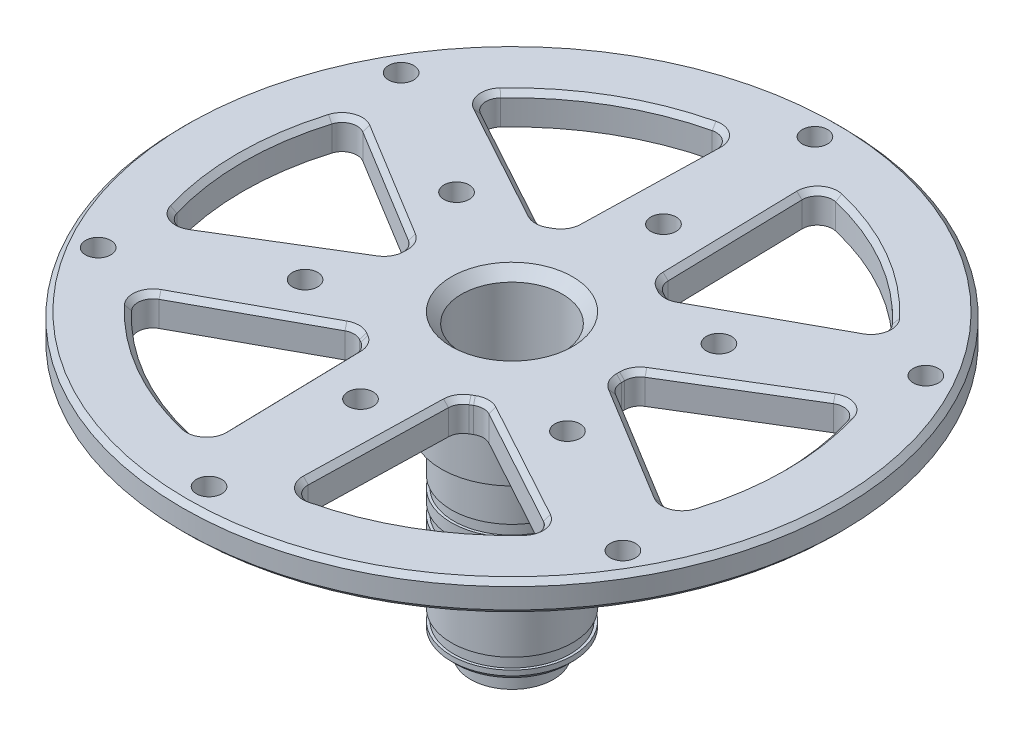
SolidWorks part; units mm, degrees
ref_plane "Front Plane" through (0, 0, 0) normal (0, 0, 1) x (1, 0, 0)
ref_plane "Top Plane" through (0, 0, 0) normal (0, 1, 0) x (1, 0, 0)
ref_plane "Right Plane" through (0, 0, 0) normal (1, 0, 0) x (0, 0, -1)
ref_axis "Axis1" through (0, 0, 0) along (0, 1, 0)
sketch "Sketch2" plane through (0, 0, 0) normal (0, 0, 1) x (1, 0, 0)
  line L0 (0, 0) -> (0, -45684.8392) construction
  line L1 (-4, 10) -> (-4, -6.5)
  line L2 (-4, -6.5) -> (-3.1, -6.5)
  line L3 (-3.1, -6.5) -> (-3.1, -9.5)
  line L4 (-3.1, -9.5) -> (-4.1, -9.5)
  line L5 (-4.1, -9.5) -> (-4.1, -7.5)
  line L6 (-4.1, -7.5) -> (-6, -7.5)
  line L7 (-6, -7.5) -> (-6, 10)
  line L9 (-11.5, -12.5) -> (11.5, -12.5) construction
  line L18 (-7, 17) -> (-7, 10)
  line L20 (-4, 10) -> (-5, 11)
  line L21 (-5, 20) -> (-32.65, 20)
  line L25 (-32.65, 17) -> (-7, 17)
  line L27 (31.65, 16) -> (-31.65, 16) construction
  line L28 (-20.098, 13.65) -> (-20.098, 18.273) construction
  line L31 (-5, 11) -> (-5, 20)
  line L37 (-7, 10) -> (-6, 10)
  line L40 (8.8, 10) -> (-8.8, 10) construction
  line L43 (-32.65, 17) -> (-32.65, 20)
  line L44 (-32.65, 15) -> (-32.65, 4) construction
  point P6 (-1.75, -8.5689)
  point P11 (0, 0)
  point P12 (0, 0)
  point P13 (-1.75, -7.3551)
  point P14 (0, 0)
  point P15 (-6, -7.9145)
  point P16 (-4, -6.8486)
  dimension "D1" = 8
  dimension "D3" = 8.2
  dimension "D4" = 12
  dimension "D5" = 2
  dimension "D6" = 1
  dimension "D7" = 1
  dimension "D8" = 2
  dimension "D9" = 5
  dimension "D10" = 1
  dimension "D12" = 3
  dimension "D13" = 1
  dimension "D15" = 20.098
  dimension "D20" = 10
  dimension "D21" = 135
revolve "Revolve1" add sketch "Sketch2" angle 360 about L0
sketch "Sketch3" plane through (0, 0, 0) normal (0, 0, 1) x (1, 0, 0)
  line L0 (-20.098, 18.273) -> (-20.098, -49187.0734) construction
  line L1 (-21.598, 15) -> (-22.598, 15)
  line L2 (-22.598, 15) -> (-22.598, 17)
  line L4 (-20.098, 17) -> (-20.098, 11)
  line L5 (-20.098, 11) -> (-21.598, 11)
  line L6 (-21.598, 15) -> (-21.598, 11)
  line L7 (-32.65, 17) -> (32.65, 17) construction
  line L8 (-22.598, 17) -> (-20.098, 17)
  line L9 (-18.398, 15) -> (-21.798, 15) construction
  dimension "D1" = 3
  dimension "D2" = 4
  dimension "D3" = 1
revolve "Revolve2" add sketch "Sketch3" angle 360 about L0
pattern_circular "CirPattern1" count 3 over 360 about axis through (0, 0, 0) along (0, 1, 0) of "Revolve2"
chamfer "Chamfer1" distance 0.5 angle 45 2 edges at (0, 20, 32.65) (0, 17, 32.65)
chamfer "Chamfer2" distance 1 angle 45 1 edges at (0, 20, 5)
sketch "Sketch6" plane through (0, 0, 0) normal (0, 1, 0) x (1, 0, 0)
  line L0 (0, 0) -> (50000, 0) construction
  line L1 (24.8992, -9.5) -> (10.9545, -1)
  line L2 (10.9545, 1) -> (24.8992, 9.5)
  arc A0 (24.8992, -9.5) -> (24.8992, 9.5) centre (0, 0) ccw
  arc A1 (10.9545, -1) -> (10.9545, 1) centre (0, 0) ccw
  circle A3 centre (0, 0) radius 32.65 construction
  circle A4 centre (0, 0) radius 7 construction
  dimension "D1" = 4
  dimension "D2" = 6
  dimension "D3" = 2
  dimension "D4" = 19
extrude "Cut-Extrude1" cut sketch "Sketch6" along normal through all
fillet "Fillet1" radius 1.5 4 edges at (24.8992, 18.5, 9.5) (10.9545, 18.5, 1) (10.9545, 18.5, -1) (24.8992, 18.5, -9.5)
hole_wizard "M3x0.5 Tapped Hole1" positions "Sketch7" profile "Sketch8" tap size "M3x0.5" standard "ANSI Metric" end condition through all
sketch "Sketch7" plane through (0, 20, 0) normal (0, 1, 0) x (1, 0, 0)
  line L0 (0, 0) -> (12.9904, -7.5) construction
  line L3 (0, 0) -> (0, -9.9462) construction
  circle A0 centre (0, 0) radius 15 construction
  circle A1 centre (0, 0) radius 30 construction
  point P2 (12.9904, -7.5)
  dimension "D1" = 60
  dimension "D2" = 30
  dimension "D3" = 60
sketch "Sketch8" plane through (12.9904, 20, 7.5) normal (1, 0, 0) x (0, 0, 1)
  line L0 (0, 0) -> (0, 29.5)
  line L1 (0, 29.5) -> (1.25, 29.5)
  line L2 (1.25, 29.5) -> (1.25, 0)
  line L5 (1.25, 0) -> (0, 0)
  line L11 (0, -6.35) -> (0, 107.95) construction
  dimension "Thru Tap Drill Dia." = 2.5
  dimension "Thru Tap Drill Depth" = 29.5
cosmetic thread "Hole Thread3" parameters "D2"=3
pattern_circular "CirPattern2" count 6 over 360 about axis through (0, 0, 0) along (0, 1, 0) of "Cut-Extrude1", "Fillet1", "M3x0.5 Tapped Hole1"
sketch "Sketch9" plane through (0, 0, 0) normal (0, 0, 1) x (1, 0, 0)
  line L0 (0, 0) -> (0, -50000) construction
  line L1 (-8.5387, -5.4) -> (-5.75, -5.4)
  line L3 (-6.5, -6.5) -> (-5.75, -6.5)
  line L4 (-5.75, -5.4) -> (-5.75, -6.5)
  line L6 (-6.5, -6.5) -> (-5.5, -7.5)
  line L7 (-5.5, -7.5) -> (-8.5387, -7.5)
  line L8 (-8.5387, -7.5) -> (-8.5387, -5.4)
  line L9 (-6, -7.5) -> (6, -7.5) construction
  line L10 (-6, 10) -> (-6, -7.5) construction
  dimension "D1" = 11.5
  dimension "D2" = 1.1
  dimension "D3" = 45
  dimension "D4" = 1
  dimension "D5" = 0.5
revolve "Cut-Revolve1" cut sketch "Sketch9" angle 360 about L0
sketch "Sketch10" plane through (0, 0, 0) normal (0, 0, 1) x (1, 0, 0)
  line L0 (0, 0) -> (0, 50000) construction
  line L1 (-6.9577, 6) -> (-5.75, 6)
  line L2 (-6.9577, 6) -> (-6.9577, 4.9)
  line L3 (-6.9577, 4.9) -> (-5.75, 4.9)
  line L4 (-5.75, 6) -> (-5.75, 4.9)
  line L5 (-9, 6) -> (9, 6) construction
  dimension "D1" = 11.5
  dimension "D2" = 1.1
revolve "Cut-Revolve2" cut sketch "Sketch10" angle 360 about L0
sketch "Sketch11" plane through (0, 0, 0) normal (0, 0, 1) x (1, 0, 0)
  line L0 (0, 0) -> (0, -50000) construction
  line L1 (-8.902, 3.7) -> (-5.75, 3.7)
  line L2 (-8.902, 3.7) -> (-8.902, 2.6)
  line L3 (-8.902, 2.6) -> (-5.75, 2.6)
  line L4 (-5.75, 3.7) -> (-5.75, 2.6)
  line L7 (8.8, 2.6) -> (-8.8, 2.6) construction
  dimension "D1" = 11.5
  dimension "D2" = 1.1
revolve "Cut-Revolve3" cut sketch "Sketch11" angle 360 about L0
hole_wizard "M3x0.5 Tapped Hole2" positions "Sketch12" profile "Sketch13" tap size "M3x0.5" standard "ANSI Metric" end condition through all
sketch "Sketch12" plane through (0, 20, 0) normal (0, 1, 0) x (1, 0, 0)
  circle A0 centre (0, 0) radius 30 construction
  point P0 (0, 30)
  dimension "D1" = 60
sketch "Sketch13" plane through (0, 20, -30) normal (1, 0, 0) x (0, 0, 1)
  line L0 (0, 0) -> (0, 29.5)
  line L1 (0, 29.5) -> (1.25, 29.5)
  line L2 (1.25, 29.5) -> (1.25, 0)
  line L5 (1.25, 0) -> (0, 0)
  line L11 (0, -6.35) -> (0, 107.95) construction
  dimension "Thru Tap Drill Dia." = 2.5
  dimension "Thru Tap Drill Depth" = 29.5
cosmetic thread "Hole Thread4" parameters "D2"=3
pattern_circular "CirPattern3" count 6 over 360 about axis through (0, 0, 0) along (0, 1, 0) of "M3x0.5 Tapped Hole2"
chamfer "Chamfer3" distance 0.5 angle 45 48 edges at (-5.5, 20, -9.5263) (-4.8052, 20, -10.1415) (-6.3802, 20, -9.2321) (-4.4284, 20, -17.6625) (-13.082, 20, -12.6664) (-4.8214, 20, -25.6448) (-19.7984, 20, -16.9978) (-13.325, 20, -23.0796) (11, 20, 0) (11.1854, 20, 0.9094) (11.1854, 20, -0.9094) (17.5104, 20, 4.9961) (17.5104, 20, -4.9961) (24.6198, 20, 8.647) (24.6198, 20, -8.647) (26.65, 20, 0) (5.5, 20, -9.5263) (6.3802, 20, -9.2321) (4.8052, 20, -10.1415) (13.082, 20, -12.6664) (4.4284, 20, -17.6625) (19.7984, 20, -16.9978) (4.8214, 20, -25.6448) (13.325, 20, -23.0796) (-17.5104, 20, -4.9961) (-24.6198, 20, -8.647) (-11.1854, 20, -0.9094) (-26.65, 20, 0) (-11, 20, 0) (-24.6198, 20, 8.647) (-11.1854, 20, 0.9094) (-17.5104, 20, 4.9961) (-13.082, 20, 12.6664) (-19.7984, 20, 16.9978) (-6.3802, 20, 9.2321) (-13.325, 20, 23.0796) (-5.5, 20, 9.5263) (-4.8214, 20, 25.6448) (-4.8052, 20, 10.1415) (-4.4284, 20, 17.6625) (13.082, 20, 12.6664) (6.3802, 20, 9.2321) (19.7984, 20, 16.9978) (5.5, 20, 9.5263) (13.325, 20, 23.0796) (4.8052, 20, 10.1415) (4.8214, 20, 25.6448) (4.4284, 20, 17.6625)
